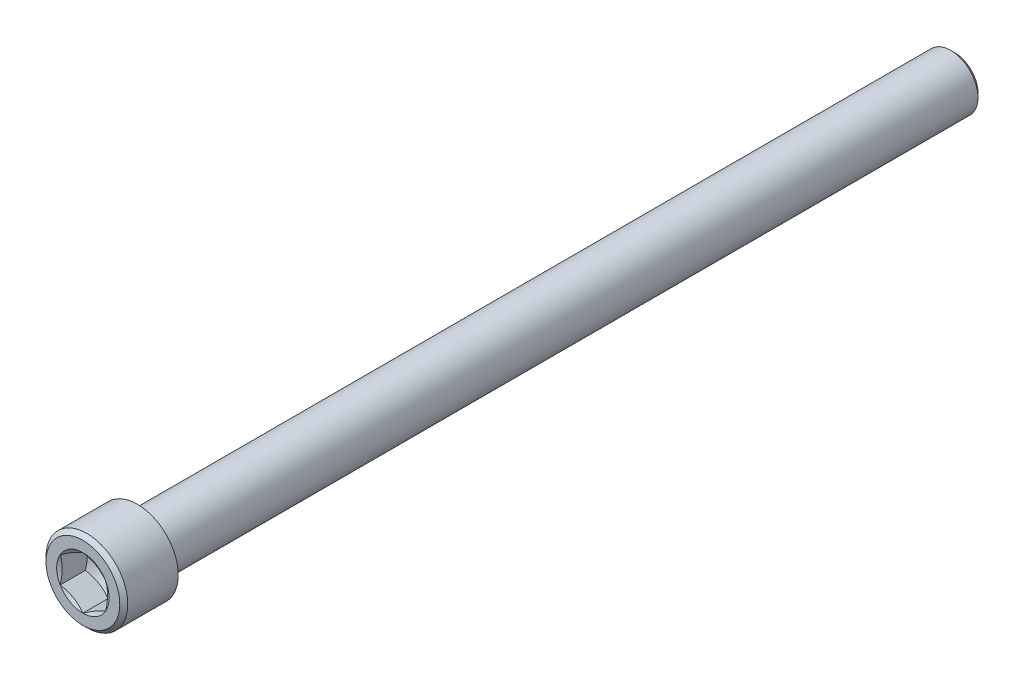
SolidWorks part; units mm, degrees
ref_plane "Front" through (0, 0, 0) normal (0, 0, 1) x (1, 0, 0)
ref_plane "Top" through (0, 0, 0) normal (0, 1, 0) x (1, 0, 0)
ref_plane "Right" through (0, 0, 0) normal (1, 0, 0) x (0, 0, -1)
sketch "Sketch1" plane through (0, 0, 0) normal (1, 0, 0) x (0, 0, -1)
  line L0 (0, 9) -> (-12, 9)
  line L1 (-12, 9) -> (-12, 0)
  line L2 (-12, 0) -> (180, 0)
  line L3 (180, 0) -> (180, 6)
  line L4 (180, 6) -> (0, 6)
  line L5 (0, 6) -> (0, 9)
  line L6 (0, 0) -> (12.7561, 0) construction
  dimension "l" = 180
  dimension "d" = 12
  dimension "k" = 12
  dimension "dk" = 18
revolve "Revolve1" add sketch "Sketch1" angle 360 about L2
cosmetic thread "Filettatura cosmetica1" parameters "D1"=179.4, "D2"=10.072
sketch "Sketch7" plane through (0, 0, 0) normal (1, 0, 0) x (0, 0, -1)
  line L0 (-6.6396, 0) -> (3.6195, 0) construction
  line L1 (-12, 0) -> (-12, 5)
  line L2 (-12, 9) -> (-12, -9) construction
  line L3 (-12, 5) -> (-6, 5)
  line L4 (-6, 5) -> (-3.1132, 0)
  line L6 (-12, 0) -> (-3.1132, 0)
  dimension "D1" = 60
  dimension "S" = 10
  dimension "t" = 6
revolve "Cut-Revolve2" cut sketch "Sketch7" angle 360 about L6
chamfer "Chamfer1" distance 0.875 2 edges at (0, -6, -180) (0, -9, 12)
sketch "Sketch8" plane through (0, 0, 12) normal (0, 0, 1) x (1, 0, 0)
  line L1 (0, 5.7735) -> (-5, 2.8868)
  line L2 (-5, 2.8868) -> (-5, -2.8868)
  line L3 (-5, -2.8868) -> (0, -5.7735)
  line L4 (0, -5.7735) -> (5, -2.8868)
  line L5 (5, -2.8868) -> (5, 2.8868)
  line L6 (5, 2.8868) -> (0, 5.7735)
  circle A0 centre (0, 0) radius 5 construction
  circle A1 centre (0, 0) radius 5 construction
extrude "Cut-Extrude1" cut sketch "Sketch8" against normal up to surface (5.5534 mm away) up to face at (5, 0, 6)
sketch "Sketch9" plane through (0, 0, 0) normal (1, 0, 0) x (0, 0, -1)
  line L0 (-12, 5) -> (4.2695, 5) construction
  line L3 (-12.5, 6.6395) -> (-12.5, 5)
  line L4 (-12.5, 5) -> (-11.5534, 5)
  line L5 (-11.5534, 5) -> (-12.5, 6.6395)
  line L6 (-12, 9) -> (-12, -9) construction
  dimension "D1" = 60
  dimension "D2" = 0.5
revolve "Cut-Revolve3" cut sketch "Sketch9" angle 360 about axis through (0, 0, 12) along (0, 0, -1)
fillet "Fillet2" radius 0.6 1 edges at (0, -6, 0)
